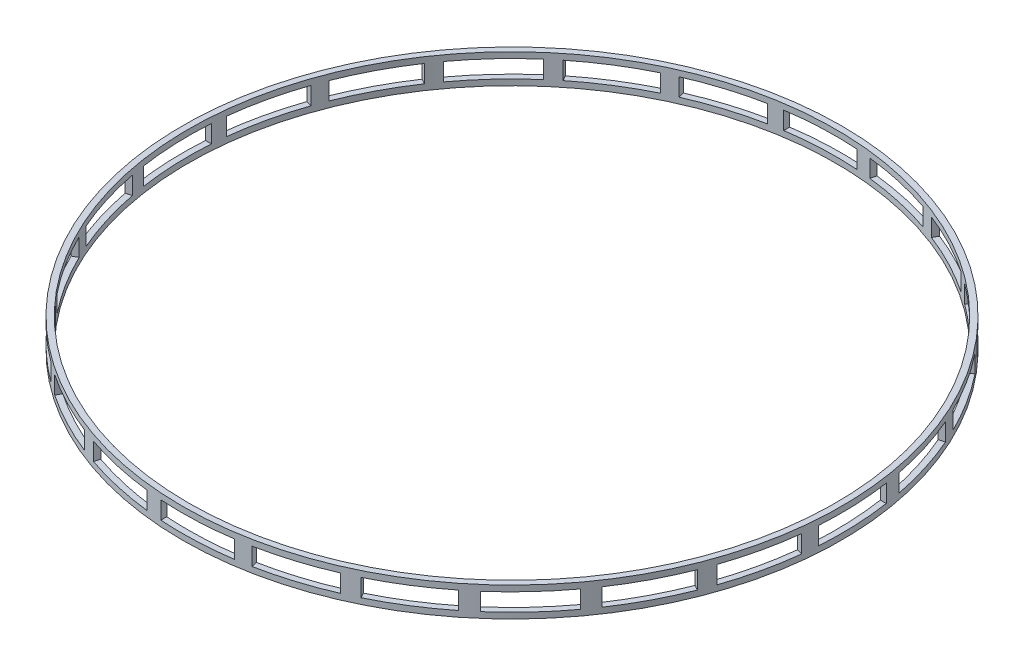
SolidWorks part; units mm, degrees
ref_plane "Front Plane" through (0, 0, 0) normal (0, 0, 1) x (1, 0, 0)
ref_plane "Top Plane" through (0, 0, 0) normal (0, 1, 0) x (1, 0, 0)
ref_plane "Right Plane" through (0, 0, 0) normal (1, 0, 0) x (0, 0, -1)
sketch "Sketch1" plane through (0, 0, 0) normal (0, 1, 0) x (1, 0, 0)
  line L0 (112, 0) -> (110, 0) construction
  line L1 (0, 112) -> (0, -112)
  line L6 (0, 0) -> (-215.0076, 0) construction
  circle A0 centre (0, 0) radius 110
  circle A1 centre (0, 0) radius 112
  dimension "D1" = 220
  dimension "D2" = 2
extrude "Boss-Extrude1" add sketch "Sketch1" along normal blind 10 contours L1 A1 A0 | A1 L1 A0 region at (79.0189, 0, -79.0189) region at (-2.5044, 0, -111)
sketch "Sketch2" plane through (0, 0, 0) normal (0, 0, 1) x (1, 0, 0)
  line L0 (-112, 0) -> (112, 0) construction
  line L1 (-16.4159, 8) -> (7.5841, 8)
  line L2 (-16.4159, 8) -> (-16.4159, 2)
  line L3 (-16.4159, 2) -> (7.5841, 2)
  line L4 (7.5841, 8) -> (7.5841, 2)
  line L5 (112, 10) -> (-112, 10) construction
  dimension "D1" = 2
  dimension "D2" = 2
  dimension "D3" = 24
extrude "Cut-Extrude1" cut sketch "Sketch2" against normal through all
ref_axis "Axis1" through (0, 10, 0) along (0, -1, 0)
pattern_circular "CirPattern1" count 24 over 360 about axis through (0, 10, 0) along (0, -1, 0) of "Cut-Extrude1"
